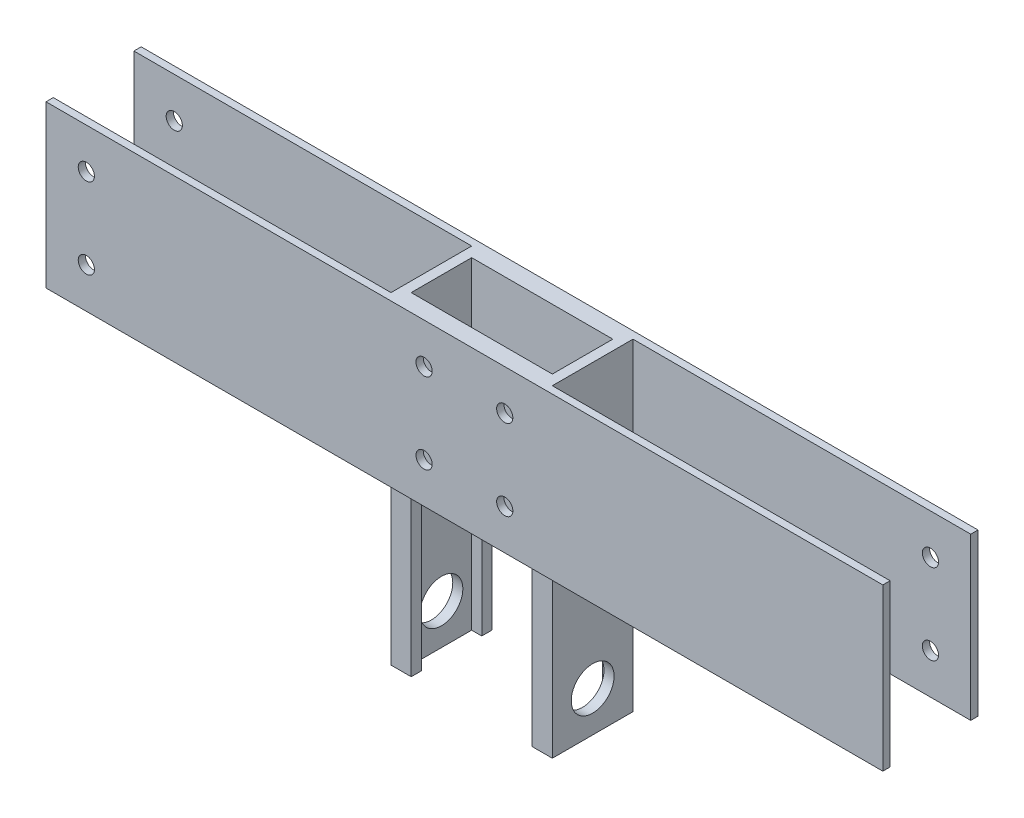
SolidWorks part; units mm, degrees
ref_plane "Front Plane" through (0, 0, 0) normal (0, 0, 1) x (1, 0, 0)
ref_plane "Top Plane" through (0, 0, 0) normal (0, 1, 0) x (1, 0, 0)
ref_plane "Right Plane" through (0, 0, 0) normal (1, 0, 0) x (0, 0, -1)
sketch "Sketch1" plane through (0, 0, 0) normal (0, 0, 1) x (1, 0, 0)
  line L0 (-131.7625, 25.4) -> (-131.7625, -25.4)
  line L1 (-131.7625, -25.4) -> (131.7625, -25.4)
  line L2 (131.7625, -25.4) -> (131.7625, 25.4)
  line L3 (131.7625, 25.4) -> (-131.7625, 25.4)
  line L4 (0, 0) -> (0, -152.4) construction
  line L5 (-25.4, 0) -> (-25.4, -152.4) construction
  line L6 (25.4, 0) -> (25.4, -152.4) construction
  line L7 (-25.4, 0) -> (25.4, 0) construction
  line L8 (-25.4, -152.4) -> (25.4, -152.4) construction
  point P4 (0, -25.4)
  point P5 (-131.7625, 0)
  dimension "D1" = 50.8
  dimension "D2" = 263.525
  dimension "D3" = 152.4
  dimension "D4" = 25.4
  dimension "D5" = 25.4
extrude "Boss-Extrude1" add sketch "Sketch1" along normal mid plane 2.286 contours L5 L7 L6 L1 L2 L3 L0 | L4 L7 L5 L1 | L7 L4 L1 L6 | L1 L4 L8 L6 | L4 L1 L5 L8 region at (0, 0, 0)
hole_wizard "#10 Clearance Hole1" positions "Sketch3" profile "Sketch2" hole size "#10" standard "ANSI Inch" end condition through all
sketch "Sketch3" plane through (0, 0, 1.143) normal (0, 0, 1) x (1, 0, 0)
  line L0 (-131.7625, 25.4) -> (-131.7625, -25.4) construction
  line L1 (131.7625, 25.4) -> (-131.7625, 25.4) construction
  line L2 (-131.7625, -25.4) -> (131.7625, -25.4) construction
  line L4 (-12.7, -12.7) -> (12.7, -12.7) construction
  line L5 (-12.7, -12.7) -> (-12.7, 12.7) construction
  line L6 (-12.7, 12.7) -> (12.7, 12.7) construction
  line L7 (12.7, -12.7) -> (12.7, 12.7) construction
  line L8 (-12.7, -12.7) -> (12.7, 12.7) construction
  line L9 (-12.7, 12.7) -> (12.7, -12.7) construction
  point P0 (-119.0625, 12.7)
  point P25 (-119.0625, -12.7)
  point P30 (-12.7, 12.7)
  point P32 (-12.7, -12.7)
  point P34 (12.7, -12.7)
  point P36 (12.7, 12.7)
  point P70 (0, 0)
  dimension "D5" = 25.4
  dimension "D1" = 12.7
  dimension "D2" = 12.7
  dimension "D4" = 12.7
  dimension "D3" = 2
sketch "Sketch2" plane through (-119.0625, 12.7, 1.143) normal (1, 0, 0) x (0, -1, 0)
  line L0 (0, 0) -> (0, 2.286)
  line L1 (0, 2.286) -> (2.5527, 2.286)
  line L2 (2.5527, 2.286) -> (2.5527, 0)
  line L5 (2.5527, 0) -> (0, 0)
  line L11 (0, -6.35) -> (0, 107.95) construction
  dimension "Thru Hole Dia." = 5.1054
  dimension "Thru Hole Depth" = 2.286
mirror "Mirror1" about plane through (0, 0, 0) normal (1, 0, 0) of "#10 Clearance Hole1"
sketch "Sketch4" plane through (0, 0, 0) normal (0, 1, 0) x (1, 0, 0)
  line L0 (-131.7625, -1.143) -> (131.7625, -1.143) construction
  line L1 (25.4, -1.143) -> (-25.4, -1.143)
  line L2 (25.4, -1.143) -> (25.4, -26.543)
  line L3 (25.4, -26.543) -> (-25.4, -26.543)
  line L4 (-25.4, -1.143) -> (-25.4, -26.543)
  line L5 (22.225, -4.318) -> (-22.225, -4.318)
  line L6 (-22.225, -4.318) -> (-22.225, -23.368)
  line L7 (22.225, -23.368) -> (-22.225, -23.368)
  line L8 (22.225, -4.318) -> (22.225, -23.368)
  point P6 (0, -26.543)
  dimension "D1" = 25.4
  dimension "D2" = 50.8
  dimension "D3" = 3.175
extrude "Boss-Extrude2" add sketch "Sketch4" along normal blind 25.4 and the other way blind 76.2
ref_plane "Plane1" through (0, 0, 13.843) normal (0, 0, 1) x (1, 0, 0)
mirror "Mirror2" about plane through (0, 0, 13.843) normal (0, 0, 1) of "#10 Clearance Hole1", "Boss-Extrude1"
sketch "Sketch5" plane through (0, 0, 26.543) normal (0, 0, 1) x (1, 0, 0)
  line L1 (19.05, -25.4) -> (-19.05, -25.4)
  line L2 (19.05, -25.4) -> (19.05, -76.2)
  line L3 (19.05, -76.2) -> (-19.05, -76.2)
  line L4 (-19.05, -25.4) -> (-19.05, -76.2)
  line L5 (-25.4, -76.2) -> (25.4, -76.2) construction
  point P6 (0, -25.4)
  dimension "D1" = 38.1
  dimension "D2" = 50.8
extrude "Cut-Extrude1" cut sketch "Sketch5" against normal through all
hole_wizard "1/2 Clearance Hole1" positions "Sketch7" profile "Sketch6" hole size "1/2" standard "ANSI Inch" end condition through all
sketch "Sketch7" plane through (25.4, 0, 0) normal (1, 0, 0) x (0, 0, -1)
  line L0 (-13.843, 3.4925) -> (-13.843, -3.4925) construction
  line L2 (-26.543, -76.2) -> (-1.143, -76.2) construction
  point P0 (-13.843, -63.5)
  dimension "D1" = 12.7
sketch "Sketch6" plane through (25.4, -63.5, 13.843) normal (0, 1, 0) x (0, 0, -1)
  line L0 (0, 0) -> (0, 157.1625)
  line L1 (0, 157.1625) -> (6.7462, 157.1625)
  line L2 (6.7462, 157.1625) -> (6.7462, 0)
  line L5 (6.7462, 0) -> (0, 0)
  line L11 (0, -6.35) -> (0, 107.95) construction
  dimension "Thru Hole Dia." = 13.4925
  dimension "Thru Hole Depth" = 157.1625
